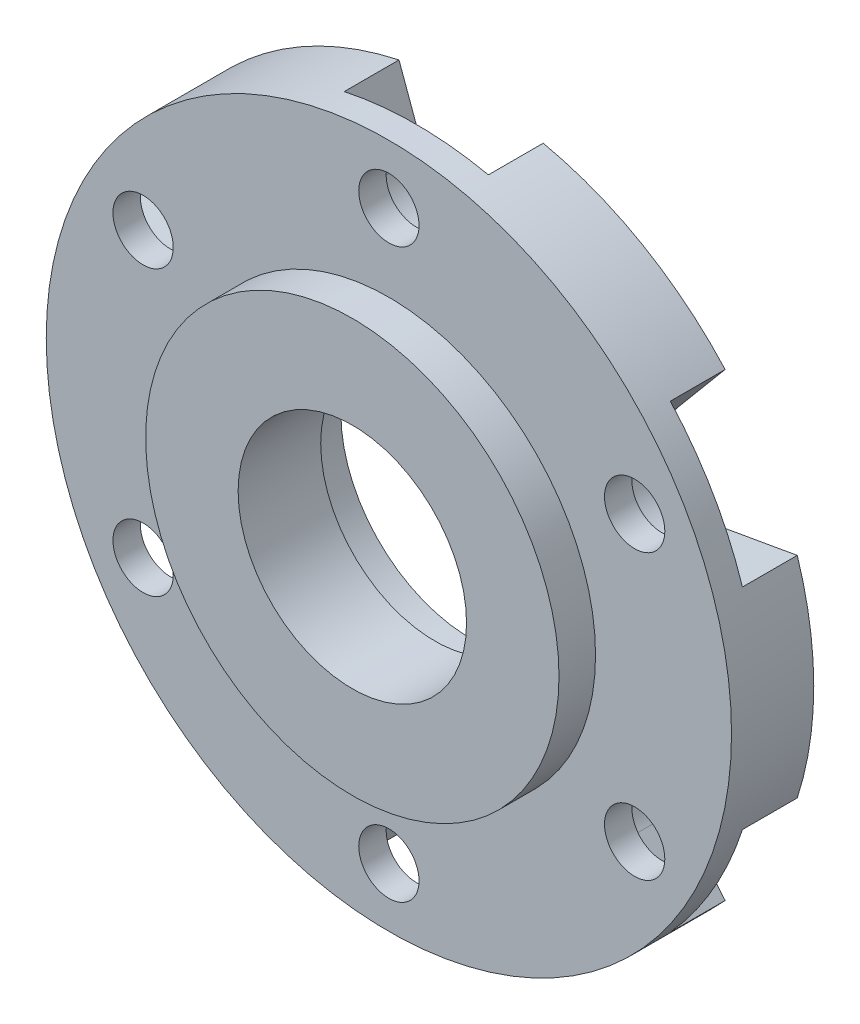
SolidWorks part; units mm, degrees
material "6061-T6 (SS)"
ref_plane "Front Plane" through (0, 0, 0) normal (0, 0, 1) x (1, 0, 0)
ref_plane "Top Plane" through (0, 0, 0) normal (0, 1, 0) x (1, 0, 0)
ref_plane "Right Plane" through (0, 0, 0) normal (1, 0, 0) x (0, 0, -1)
sketch "Sketch Spindle Skeleton" plane through (0, 0, 0) normal (1, 0, 0) x (0, 0, -1)
  line L0 (-108, -9.5) -> (-149, -9.5)
  line L5 (-1000, 0) -> (49000, 0)
  line L6 (0, -9.5) -> (0, 9.5)
  line L13 (0, 9.5) -> (-46.4, 9.5)
  line L26 (-46.4, 9.5) -> (-46.4, 14)
  line L27 (-46.4, 14) -> (-108, 14)
  line L32 (-108, 14) -> (-108, 9.5)
  line L34 (-165, 7) -> (-165, -7)
  line L36 (-108, -9.5) -> (-108, -14)
  line L37 (-108, -14) -> (-46.4, -14)
  line L38 (-46.4, -14) -> (-46.4, -9.5)
  line L39 (0, -9.5) -> (-46.4, -9.5)
  line L40 (-22.625, 37.5) -> (-13.625, 37.5)
  line L41 (-124.6, 22.6187) -> (-108, 22.6187)
  line L42 (-124.6, 22.6187) -> (-124.6, -22.6187)
  line L43 (-124.6, -22.6187) -> (-108, -22.6187)
  line L44 (-108, 22.6187) -> (-108, -22.6187)
  line L45 (-124.6, 22.6187) -> (-108, -22.6187) construction
  line L46 (-124.6, -22.6187) -> (-108, 22.6187) construction
  line L47 (-29.8, 22.6187) -> (-46.4, 22.6187)
  line L48 (-29.8, 22.6187) -> (-29.8, -22.6187)
  line L49 (-29.8, -22.6187) -> (-46.4, -22.6187)
  line L50 (-46.4, 22.6187) -> (-46.4, -22.6187)
  line L51 (-29.8, 22.6187) -> (-46.4, -22.6187) construction
  line L52 (-29.8, -22.6187) -> (-46.4, 22.6187) construction
  line L59 (-13.625, 37.5) -> (-13.625, -37.5)
  line L60 (-13.625, -37.5) -> (-22.625, -37.5)
  line L61 (-22.625, -22.6187) -> (-26.625, -22.6187)
  line L62 (-26.625, -22.6187) -> (-26.625, -12.5)
  line L63 (-26.625, -12.5) -> (-22.625, -12.5)
  line L64 (-22.625, -12.5) -> (-22.625, 12.5)
  line L65 (-22.625, 12.5) -> (-26.625, 12.5)
  line L66 (-26.625, 12.5) -> (-26.625, 22.6187)
  line L67 (-26.625, 22.6187) -> (-22.625, 22.6187)
  line L68 (-22.625, 22.6187) -> (-22.625, 37.5)
  line L69 (-22.625, -22.6187) -> (-22.625, -37.5)
  line L71 (-136.284, 37.5) -> (-23.625, 37.5)
  line L72 (-136.284, 37.5) -> (-136.284, -37.5)
  line L73 (-136.284, -37.5) -> (-23.625, -37.5)
  line L74 (-23.625, 37.5) -> (-23.625, -37.5)
  line L75 (-136.284, 37.5) -> (-23.625, -37.5) construction
  line L76 (-136.284, -37.5) -> (-23.625, 37.5) construction
  line L77 (-149, -9.5) -> (-149, -7)
  line L78 (-149, -7) -> (-165, -7)
  line L79 (-108, 9.5) -> (-149, 9.5)
  line L80 (-149, 7) -> (-165, 7)
  line L81 (-149, 9.5) -> (-149, 7)
  line L82 (-128.5, 9.5) -> (-128.5, -9.5) construction
  line L83 (-23.2, 9.5) -> (-23.2, -9.5) construction
  line L96 (-136.284, 37.5) -> (-145.284, 37.5)
  line L98 (-136.284, -37.5) -> (-145.284, -37.5)
  line L99 (-145.284, 37.5) -> (-145.284, -37.5)
  line L110 (-136.284, 37.5) -> (-136.284, -37.5)
  point P3 (0, 0)
  point P18 (-116.3, 0)
  point P24 (-38.1, 0)
  point P29 (-79.9545, 0)
  point P48 (-13.625, 31.0593)
  point P70 (-145.284, 31.0593)
revolve "Main Revolve" add sketch "Sketch Spindle Skeleton" angle 360 about L5 region at (0, 23.2707, 18.318) region at (0, 17.5594, 25.125)
sketch "Sketch Center Cut" plane through (0, 0, 22.625) normal (0, 0, 1) x (1, 0, 0)
  circle A3 centre (0, 0) radius 12.5
  dimension "D1" = 25
extrude "Cut Center" cut sketch "Sketch Center Cut" against normal through all both and the other way through all
hole_wizard "CBORE for M6 SHCS1" positions "Hole wizard sketch 1" profile "Hole wizard sketch 2" counterbore size "M6" standard "ANSI Metric" end condition through all
sketch "Hole wizard sketch 1" plane through (0, 0, 13.625) normal (0, 0, -1) x (-1, 0, 0)
  point P0 (0, 31.0593)
sketch "Hole wizard sketch 2" plane through (0, 31.0593, 13.625) normal (1, 0, 0) x (0, 1, 0)
  line L0 (0, 0) -> (0, 13)
  line L1 (0, 13) -> (3.3, 13)
  line L3 (3.3, 13) -> (3.3, 6)
  line L4 (3.3, 6) -> (5.5, 6)
  line L5 (5.5, 6) -> (5.5, 0)
  line L7 (5.5, 0) -> (0, 0)
  line L11 (0, -6.35) -> (0, 107.95) construction
  dimension "Thru Hole Dia." = 6.6
  dimension "Thru Hole Depth" = 13
  dimension "C'Bore Dia." = 11
  dimension "C'Bore Depth" = 6
pattern_circular "CirPattern1" count 6 over 360 about axis through (0, 0, 13.625) along (0, 0, 1) of "CBORE for M6 SHCS1"
sketch "Sketch1" plane through (0, 0, 13.625) normal (0, 0, -1) x (-1, 0, 0)
  circle A0 centre (0, 0) radius 14.2558
  dimension "D1" = 28.5115
extrude "Cut-Extrude1" cut sketch "Sketch1" against normal blind 3.9624
sketch "Sketch2" plane through (0, 0, 13.625) normal (0, 0, -1) x (-1, 0, 0)
  line L0 (-5.1683, 29.1782) -> (-7.8915, 36.6602)
  line L1 (0, 31.0593) -> (0, 37.5) construction
  line L2 (5.1683, 29.1782) -> (7.8915, 36.6602)
  line L3 (22.6849, 19.065) -> (27.8029, 25.1644)
  line L4 (27.8533, 10.1132) -> (35.6945, 11.4959)
  line L5 (27.8533, -10.1132) -> (35.6945, -11.4959)
  line L6 (22.6849, -19.065) -> (27.8029, -25.1644)
  line L7 (5.1683, -29.1782) -> (7.8915, -36.6602)
  line L8 (-5.1683, -29.1782) -> (-7.8915, -36.6602)
  line L9 (-22.6849, -19.065) -> (-27.8029, -25.1644)
  line L10 (-27.8533, -10.1132) -> (-35.6945, -11.4959)
  line L11 (-27.8533, 10.1132) -> (-35.6945, 11.4959)
  line L12 (-22.6849, 19.065) -> (-27.8029, 25.1644)
  circle A0 centre (0, 31.0593) radius 5.5 construction
  circle A1 centre (0, 0) radius 37.5 construction
  arc A2 (-5.1683, 29.1782) -> (5.1683, 29.1782) centre (0, 31.0593) ccw
  circle A3 centre (0, 0) radius 37.5
  arc A4 (22.6849, 19.065) -> (27.8533, 10.1132) centre (26.8982, 15.5297) ccw
  arc A5 (27.8533, -10.1132) -> (22.6849, -19.065) centre (26.8982, -15.5297) ccw
  arc A6 (5.1683, -29.1782) -> (-5.1683, -29.1782) centre (0, -31.0593) ccw
  arc A7 (-22.6849, -19.065) -> (-27.8533, -10.1132) centre (-26.8982, -15.5297) ccw
  arc A8 (-27.8533, 10.1132) -> (-22.6849, 19.065) centre (-26.8982, 15.5297) ccw
  point P37 (0, 0)
  circle M3 centre (-26.8982, 15.5297) radius 5.5
  circle M4 centre (-26.8982, -15.5297) radius 5.5
  circle M5 centre (0, -31.0593) radius 5.5
  circle M6 centre (26.8982, -15.5297) radius 5.5
  circle M7 centre (26.8982, 15.5297) radius 5.5
  circle M8 centre (0, 31.0593) radius 5.5
  circle M9 centre (0, 0) radius 37.5
  dimension "D1" = 20
  dimension "D2" = 6
extrude "Cut-Extrude2" cut sketch "Sketch2" against normal up to surface (6 mm away) contours M8 | L1 L2 M8 M9 | L1 A3 L0 M8 | L4 L3 M7 M9 | M7 | L6 L5 M6 M9 | M6 | M5 | L8 L7 M5 M9 | L10 L9 M4 M9 | M4 | L12 L11 M3 M9 | A3 M3 region at (4.3779, 34.1248, 13.625) region at (4.7535, 35.3844, 13.625) region at (-4.7535, 35.3844, 13.625) region at (25.3963, 21.9868, 13.625) region at (26.8982, 15.5297, 13.625) region at (-32.3037, 18.6505, 13.625) region at (31.7393, -11.0005, 13.625) region at (-26.8982, 15.5297, 13.625) region at (26.8982, -15.5297, 13.625) region at (6.3623, -32.9803, 13.625) region at (-32.3037, -18.6505, 13.625) region at (0, -31.0593, 13.625) region at (-26.8982, -15.5297, 13.625) up to face at (23.5982, -15.5297, 19.625)
